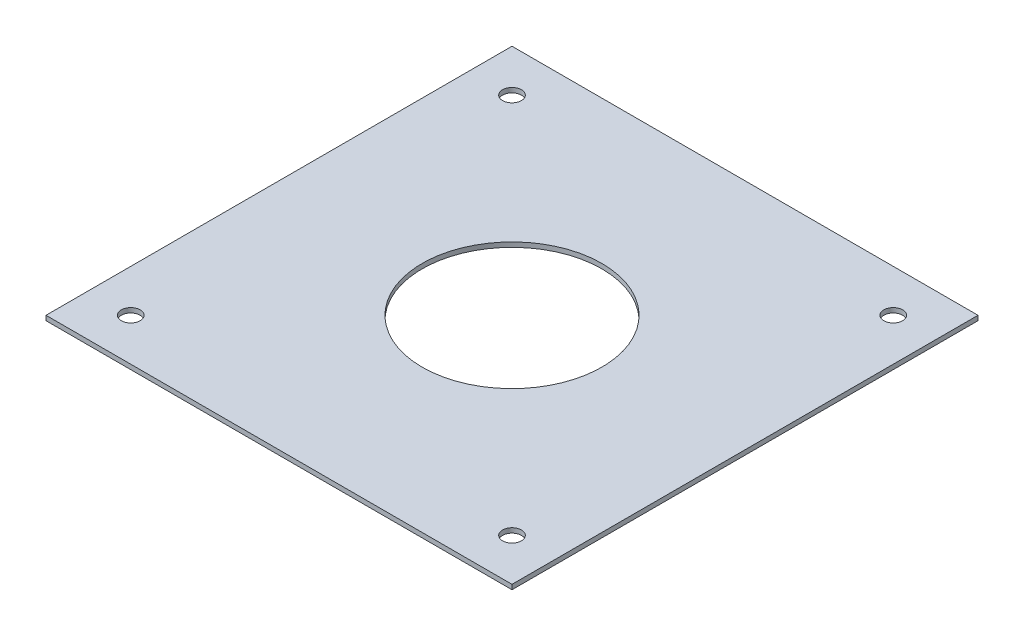
SolidWorks part; units mm, degrees
ref_plane "Front Plane" through (0, 0, 0) normal (0, 0, 1) x (1, 0, 0)
ref_plane "Top Plane" through (0, 0, 0) normal (0, 1, 0) x (1, 0, 0)
ref_plane "Right Plane" through (0, 0, 0) normal (1, 0, 0) x (0, 0, -1)
sketch "Sketch1" plane through (0, 0, 0) normal (0, 1, 0) x (1, 0, 0)
  line L1 (-49.3914, -49.3914) -> (49.3914, -49.3914)
  line L2 (-49.3914, -49.3914) -> (-49.3914, 49.3914)
  line L3 (-49.3914, 49.3914) -> (49.3914, 49.3914)
  line L4 (49.3914, -49.3914) -> (49.3914, 49.3914)
  line L5 (-49.3914, -49.3914) -> (49.3914, 49.3914) construction
  line L6 (-49.3914, 49.3914) -> (49.3914, -49.3914) construction
  point P0 (0, 0)
  dimension "D1" = 139.7
extrude "Boss-Extrude1" add sketch "Sketch1" along normal blind 1
sketch "Sketch3" plane through (0, 0, 0) normal (0, 1, 0) x (1, 0, 0)
  line L0 (-49.3914, -49.3914) -> (49.3914, 49.3914) construction
  line L1 (-40.4112, 40.4112) -> (40.4112, -40.4112) construction
  circle A0 centre (40.4112, 40.4112) radius 2
  circle A1 centre (40.4112, -40.4112) radius 2
  circle A2 centre (-40.4112, -40.4112) radius 2
  circle A3 centre (-40.4112, 40.4112) radius 2
  point P15 (0, 0)
  dimension "D3" = 4
  dimension "D2" = 114.3
  dimension "D1" = 4
extrude "Cut-Extrude2" cut sketch "Sketch3" along normal through all
sketch "Sketch8" plane through (0, 0, 0) normal (0, 1, 0) x (1, 0, 0)
  circle A0 centre (0, 0) radius 19.05 construction
  circle A1 centre (0, 0) radius 19.05
extrude "Cut-Extrude9" cut sketch "Sketch8" along normal through all
equation "\"D1@Boss-Extrude1\"=1mm"
equation "\"D3@Sketch3\"=4mm"
